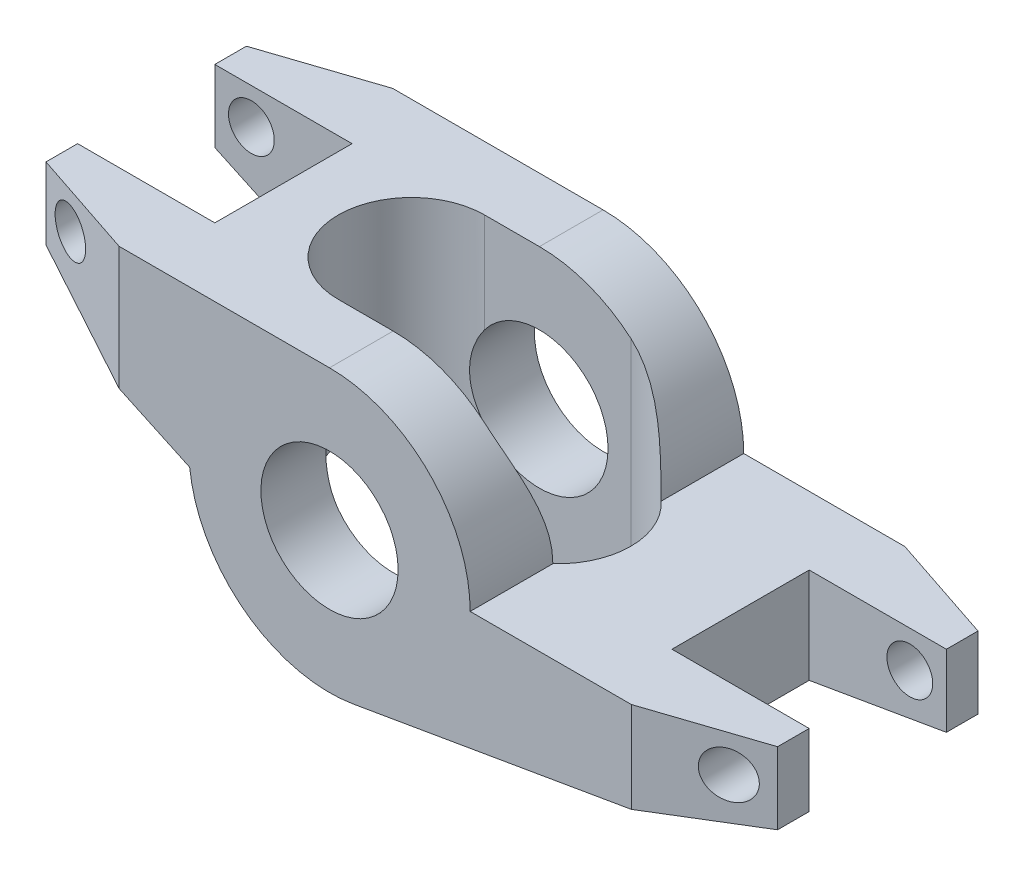
SolidWorks part; units mm, degrees
ref_plane "Front Plane" through (0, 0, 0) normal (0, 0, 1) x (1, 0, 0)
ref_plane "Top Plane" through (0, 0, 0) normal (0, 1, 0) x (1, 0, 0)
ref_plane "Right Plane" through (0, 0, 0) normal (1, 0, 0) x (0, 0, -1)
sketch "Sketch1" plane through (0, 0, 0) normal (0, 0, 1) x (1, 0, 0)
  line L0 (0, 9.77) -> (-22.23, 9.77)
  line L1 (-22.23, 9.77) -> (-22.23, 4.77)
  line L2 (-22.23, 4.77) -> (-9.7115, -1.0675)
  line L3 (9.77, 0) -> (28.58, 0)
  line L4 (28.58, 0) -> (28.58, -5)
  line L5 (28.58, -5) -> (1.6553, -9.6287)
  arc A0 (-9.7115, -1.0675) -> (1.6553, -9.6287) centre (0, 0) ccw
  circle A1 centre (0, 0) radius 4.765
  circle A3 centre (-19.69, 7.27) radius 1.59
  circle A4 centre (26.04, -2.54) radius 1.59
  arc A5 (9.77, 0) -> (0, 9.77) centre (0, 0) ccw
  point P18 (-22.23, 7.27)
  dimension "D1" = 9.53
  dimension "D2" = 19.54
  dimension "D7" = 3.18
  dimension "D12" = 3.18
  dimension "D3" = 5
  dimension "D4" = 22.23
  dimension "D5" = 25
  dimension "D6" = 2.54
  dimension "D8" = 5
  dimension "D9" = 28.58
  dimension "D10" = 2.54
  dimension "D11" = 2.54
extrude "Boss-Extrude1" add sketch "Sketch1" along normal mid plane 19
sketch "Sketch2" plane through (0, 0, 0) normal (0, 1, 0) x (1, 0, 0)
  line L0 (28.58, -9.5) -> (28.58, 9.5) construction
  line L5 (-22.23, -9.5) -> (-22.23, 9.5) construction
  line L6 (-22.23, 4.765) -> (-12.7, 4.765)
  line L7 (-22.23, 4.765) -> (-22.23, -4.765)
  line L8 (-22.23, -4.765) -> (-12.7, -4.765)
  line L9 (-12.7, 4.765) -> (-12.7, -4.765)
  line L10 (28.58, 4.765) -> (19.05, 4.765)
  line L15 (-3.81, 0) -> (6.35, 0) construction
  line L16 (-3.81, 5.08) -> (6.35, 5.08)
  line L17 (-3.81, -5.08) -> (6.35, -5.08)
  line L18 (28.58, 4.765) -> (28.58, -4.765)
  line L19 (28.58, -4.765) -> (19.05, -4.765)
  line L20 (19.05, 4.765) -> (19.05, -4.765)
  arc A0 (-3.81, 5.08) -> (-3.81, -5.08) centre (-3.81, 0) ccw
  arc A1 (6.35, -5.08) -> (6.35, 5.08) centre (6.35, 0) ccw
  point P8 (1.27, 0)
  point P13 (-22.23, 0)
  point P20 (19.05, 0)
  dimension "D5" = 5.08
  dimension "D1" = 9.53
  dimension "D2" = 9.53
  dimension "D3" = 8.89
  dimension "D4" = 10.16
extrude "Cut-Extrude1" cut sketch "Sketch2" against normal through all both and the other way through all
chamfer "Chamfer1" distance 2.54 distance2 7.62 1 edges at (28.58, -2.5, 9.5) first distance on face at (28.58, -2.5, 7.1325)
chamfer "Chamfer2" distance 2.54 distance2 7.62 1 edges at (-22.23, 7.27, 9.5) first distance on face at (-22.23, 7.27, 7.1325)
chamfer "Chamfer4" distance 7.62 distance2 2.54 1 edges at (-22.23, 7.27, -9.5) first distance on face at (1.8234, 1.0227, -9.5)
chamfer "Chamfer5" distance 7.62 distance2 2.54 1 edges at (28.58, -2.5, -9.5) first distance on face at (3.7284, 0.5785, -9.5)
